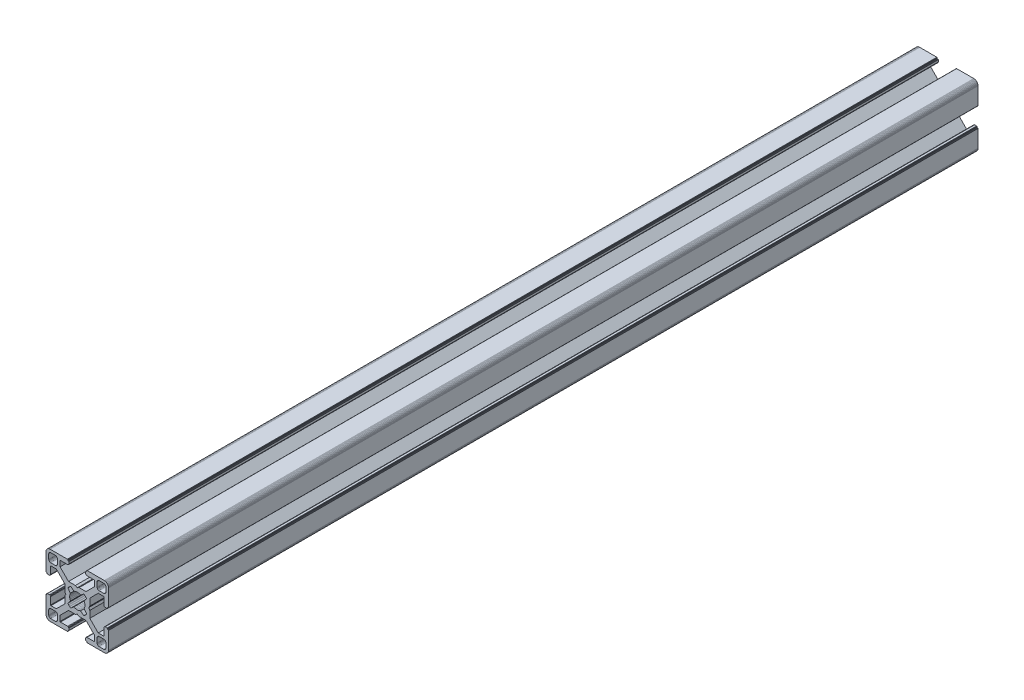
SolidWorks part; units mm, degrees
ref_plane "Front Plane" through (0, 0, 0) normal (0, 0, 1) x (1, 0, 0)
ref_plane "Top Plane" through (0, 0, 0) normal (0, 1, 0) x (1, 0, 0)
ref_plane "Right Plane" through (0, 0, 0) normal (1, 0, 0) x (0, 0, -1)
ref_plane "Plane1" through (0, 0, 0) normal (0, 0, 1) x (1, 0, 0)
sketch "Sketch1" plane through (0, 0, 0) normal (0, 0, 1) x (1, 0, 0)
  line L0 (28.3473, 29.9696) -> (28, 30)
  line L1 (28, 30) -> (19.75, 30)
  line L2 (19.75, 30) -> (19.7153, 29.997)
  line L3 (19.7153, 29.997) -> (19.6816, 29.9879)
  line L4 (19.6816, 29.9879) -> (19.65, 29.9732)
  line L5 (19.65, 29.9732) -> (19.6214, 29.9532)
  line L6 (19.6214, 29.9532) -> (19.5968, 29.9286)
  line L7 (19.5968, 29.9286) -> (19.5768, 29.9)
  line L8 (19.5768, 29.9) -> (19.5621, 29.8684)
  line L9 (19.5621, 29.8684) -> (19.553, 29.8347)
  line L10 (19.553, 29.8347) -> (19.55, 29.8)
  line L11 (19.55, 29.8) -> (19.55, 29.7)
  line L12 (19.55, 29.7) -> (19.547, 29.6653)
  line L13 (19.547, 29.6653) -> (19.5379, 29.6316)
  line L14 (19.5379, 29.6316) -> (19.5232, 29.6)
  line L15 (19.5232, 29.6) -> (19.5032, 29.5714)
  line L16 (19.5032, 29.5714) -> (19.4786, 29.5468)
  line L17 (19.4786, 29.5468) -> (19.45, 29.5268)
  line L18 (19.45, 29.5268) -> (19.4184, 29.5121)
  line L19 (19.4184, 29.5121) -> (19.3847, 29.503)
  line L20 (19.3847, 29.503) -> (19.35, 29.5)
  line L21 (19.35, 29.5) -> (19.25, 29.5)
  line L22 (19.25, 29.5) -> (19.2153, 29.497)
  line L23 (19.2153, 29.497) -> (19.1816, 29.4879)
  line L24 (19.1816, 29.4879) -> (19.15, 29.4732)
  line L25 (19.15, 29.4732) -> (19.1214, 29.4532)
  line L26 (19.1214, 29.4532) -> (19.0968, 29.4286)
  line L27 (19.0968, 29.4286) -> (19.0768, 29.4)
  line L28 (19.0768, 29.4) -> (19.0621, 29.3684)
  line L29 (19.0621, 29.3684) -> (19.053, 29.3347)
  line L30 (19.053, 29.3347) -> (19.05, 29.3)
  line L31 (19.05, 29.3) -> (19.05, 28.4)
  line L32 (19.05, 28.4) -> (19.0591, 28.2958)
  line L33 (19.0591, 28.2958) -> (19.0862, 28.1948)
  line L34 (19.0862, 28.1948) -> (19.1304, 28.1)
  line L35 (19.1304, 28.1) -> (19.1904, 28.0143)
  line L36 (19.1904, 28.0143) -> (19.2643, 27.9404)
  line L37 (19.2643, 27.9404) -> (19.35, 27.8804)
  line L38 (19.35, 27.8804) -> (19.4448, 27.8362)
  line L39 (19.4448, 27.8362) -> (19.5458, 27.8091)
  line L40 (19.5458, 27.8091) -> (19.65, 27.8)
  line L41 (19.65, 27.8) -> (23.05, 27.8)
  line L42 (23.05, 27.8) -> (23.0847, 27.7969)
  line L43 (23.0847, 27.7969) -> (23.1184, 27.7879)
  line L44 (23.1184, 27.7879) -> (23.15, 27.7732)
  line L45 (23.15, 27.7732) -> (23.1786, 27.7532)
  line L46 (23.1786, 27.7532) -> (23.2032, 27.7285)
  line L47 (23.2032, 27.7285) -> (23.2232, 27.7)
  line L48 (23.2232, 27.7) -> (23.2379, 27.6684)
  line L49 (23.2379, 27.6684) -> (23.247, 27.6347)
  line L50 (23.247, 27.6347) -> (23.25, 27.6)
  line L51 (23.25, 27.6) -> (23.25, 25.05)
  line L52 (23.25, 25.05) -> (19.2045, 21)
  line L53 (19.2045, 21) -> (15.9, 21)
  line L54 (15.9, 21) -> (15, 20.4848)
  line L55 (15, 20.4848) -> (14.1, 21)
  line L56 (14.1, 21) -> (10.7955, 21)
  line L57 (10.7955, 21) -> (7.9973, 23.8013)
  line L58 (7.9973, 23.8013) -> (6.75, 25.05)
  line L59 (6.75, 25.05) -> (6.75, 27.6)
  line L60 (6.75, 27.6) -> (6.753, 27.6347)
  line L61 (6.753, 27.6347) -> (6.7621, 27.6684)
  line L62 (6.7621, 27.6684) -> (6.7768, 27.7)
  line L63 (6.7768, 27.7) -> (6.7968, 27.7285)
  line L64 (6.7968, 27.7285) -> (6.8215, 27.7532)
  line L65 (6.8215, 27.7532) -> (6.85, 27.7732)
  line L66 (6.85, 27.7732) -> (6.8816, 27.7879)
  line L67 (6.8816, 27.7879) -> (6.9153, 27.7969)
  line L68 (6.9153, 27.7969) -> (6.95, 27.8)
  line L69 (6.95, 27.8) -> (10.35, 27.8)
  line L70 (10.35, 27.8) -> (10.4542, 27.8091)
  line L71 (10.4542, 27.8091) -> (10.5552, 27.8362)
  line L72 (10.5552, 27.8362) -> (10.65, 27.8804)
  line L73 (10.65, 27.8804) -> (10.7357, 27.9404)
  line L74 (10.7357, 27.9404) -> (10.8096, 28.0143)
  line L75 (10.8096, 28.0143) -> (10.8696, 28.1)
  line L76 (10.8696, 28.1) -> (10.9138, 28.1948)
  line L77 (10.9138, 28.1948) -> (10.9409, 28.2958)
  line L78 (10.9409, 28.2958) -> (10.95, 28.4)
  line L79 (10.95, 28.4) -> (10.95, 29.3)
  line L80 (10.95, 29.3) -> (10.947, 29.3347)
  line L81 (10.947, 29.3347) -> (10.938, 29.3684)
  line L82 (10.938, 29.3684) -> (10.9232, 29.4)
  line L83 (10.9232, 29.4) -> (10.9032, 29.4286)
  line L84 (10.9032, 29.4286) -> (10.8786, 29.4532)
  line L85 (10.8786, 29.4532) -> (10.85, 29.4732)
  line L86 (10.85, 29.4732) -> (10.8184, 29.4879)
  line L87 (10.8184, 29.4879) -> (10.7847, 29.497)
  line L88 (10.7847, 29.497) -> (10.75, 29.5)
  line L89 (10.75, 29.5) -> (10.65, 29.5)
  line L90 (10.65, 29.5) -> (10.6153, 29.503)
  line L91 (10.6153, 29.503) -> (10.5816, 29.5121)
  line L92 (10.5816, 29.5121) -> (10.55, 29.5268)
  line L93 (10.55, 29.5268) -> (10.5214, 29.5468)
  line L94 (10.5214, 29.5468) -> (10.4968, 29.5714)
  line L95 (10.4968, 29.5714) -> (10.4768, 29.6)
  line L96 (10.4768, 29.6) -> (10.4621, 29.6316)
  line L97 (10.4621, 29.6316) -> (10.453, 29.6653)
  line L98 (10.453, 29.6653) -> (10.45, 29.7)
  line L99 (10.45, 29.7) -> (10.45, 29.8)
  line L100 (10.45, 29.8) -> (10.447, 29.8347)
  line L101 (10.447, 29.8347) -> (10.4379, 29.8684)
  line L102 (10.4379, 29.8684) -> (10.4232, 29.9)
  line L103 (10.4232, 29.9) -> (10.4032, 29.9286)
  line L104 (10.4032, 29.9286) -> (10.3786, 29.9532)
  line L105 (10.3786, 29.9532) -> (10.35, 29.9732)
  line L106 (10.35, 29.9732) -> (10.3184, 29.9879)
  line L107 (10.3184, 29.9879) -> (10.2847, 29.997)
  line L108 (10.2847, 29.997) -> (10.25, 30)
  line L109 (10.25, 30) -> (2, 30)
  line L110 (2, 30) -> (1.6527, 29.9696)
  line L111 (1.6527, 29.9696) -> (1.316, 29.8794)
  line L112 (1.316, 29.8794) -> (1, 29.7321)
  line L113 (1, 29.7321) -> (0.7144, 29.5321)
  line L114 (0.7144, 29.5321) -> (0.4679, 29.2856)
  line L115 (0.4679, 29.2856) -> (0.2679, 29)
  line L116 (0.2679, 29) -> (0.1206, 28.684)
  line L117 (0.1206, 28.684) -> (0.0304, 28.3473)
  line L118 (0.0304, 28.3473) -> (0, 28)
  line L119 (0, 28) -> (0, 19.75)
  line L120 (0, 19.75) -> (0.003, 19.7153)
  line L121 (0.003, 19.7153) -> (0.0121, 19.6816)
  line L122 (0.0121, 19.6816) -> (0.0268, 19.65)
  line L123 (0.0268, 19.65) -> (0.0468, 19.6214)
  line L124 (0.0468, 19.6214) -> (0.0714, 19.5968)
  line L125 (0.0714, 19.5968) -> (0.1, 19.5768)
  line L126 (0.1, 19.5768) -> (0.1316, 19.5621)
  line L127 (0.1316, 19.5621) -> (0.1653, 19.553)
  line L128 (0.1653, 19.553) -> (0.2, 19.55)
  line L129 (0.2, 19.55) -> (0.3, 19.55)
  line L130 (0.3, 19.55) -> (0.3347, 19.547)
  line L131 (0.3347, 19.547) -> (0.3684, 19.5379)
  line L132 (0.3684, 19.5379) -> (0.4, 19.5232)
  line L133 (0.4, 19.5232) -> (0.4286, 19.5032)
  line L134 (0.4286, 19.5032) -> (0.4532, 19.4786)
  line L135 (0.4532, 19.4786) -> (0.4732, 19.45)
  line L136 (0.4732, 19.45) -> (0.4879, 19.4184)
  line L137 (0.4879, 19.4184) -> (0.497, 19.3847)
  line L138 (0.497, 19.3847) -> (0.5, 19.35)
  line L139 (0.5, 19.35) -> (0.5, 19.25)
  line L140 (0.5, 19.25) -> (0.503, 19.2153)
  line L141 (0.503, 19.2153) -> (0.5121, 19.1816)
  line L142 (0.5121, 19.1816) -> (0.5268, 19.15)
  line L143 (0.5268, 19.15) -> (0.5468, 19.1214)
  line L144 (0.5468, 19.1214) -> (0.5714, 19.0968)
  line L145 (0.5714, 19.0968) -> (0.6, 19.0768)
  line L146 (0.6, 19.0768) -> (0.6316, 19.0621)
  line L147 (0.6316, 19.0621) -> (0.6653, 19.053)
  line L148 (0.6653, 19.053) -> (0.7, 19.05)
  line L149 (0.7, 19.05) -> (1.6, 19.05)
  line L150 (1.6, 19.05) -> (1.7042, 19.0591)
  line L151 (1.7042, 19.0591) -> (1.8052, 19.0862)
  line L152 (1.8052, 19.0862) -> (1.9, 19.1304)
  line L153 (1.9, 19.1304) -> (1.9857, 19.1904)
  line L154 (1.9857, 19.1904) -> (2.0596, 19.2643)
  line L155 (2.0596, 19.2643) -> (2.1196, 19.35)
  line L156 (2.1196, 19.35) -> (2.1638, 19.4448)
  line L157 (2.1638, 19.4448) -> (2.1909, 19.5458)
  line L158 (2.1909, 19.5458) -> (2.2, 19.65)
  line L159 (2.2, 19.65) -> (2.2, 23.05)
  line L160 (2.2, 23.05) -> (2.203, 23.0847)
  line L161 (2.203, 23.0847) -> (2.2121, 23.1184)
  line L162 (2.2121, 23.1184) -> (2.2268, 23.15)
  line L163 (2.2268, 23.15) -> (2.2468, 23.1786)
  line L164 (2.2468, 23.1786) -> (2.2714, 23.2032)
  line L165 (2.2714, 23.2032) -> (2.3, 23.2232)
  line L166 (2.3, 23.2232) -> (2.3316, 23.2379)
  line L167 (2.3316, 23.2379) -> (2.3653, 23.247)
  line L168 (2.3653, 23.247) -> (2.4, 23.25)
  line L169 (2.4, 23.25) -> (4.95, 23.25)
  line L170 (4.95, 23.25) -> (7.9973, 20.2027)
  line L171 (7.9973, 20.2027) -> (8.9955, 19.2045)
  line L172 (8.9955, 19.2045) -> (8.9955, 15.9)
  line L173 (8.9955, 15.9) -> (9.5151, 15)
  line L174 (9.5151, 15) -> (8.9955, 14.1)
  line L175 (8.9955, 14.1) -> (8.9955, 10.7955)
  line L176 (8.9955, 10.7955) -> (4.95, 6.75)
  line L177 (4.95, 6.75) -> (2.4, 6.75)
  line L178 (2.4, 6.75) -> (2.3653, 6.753)
  line L179 (2.3653, 6.753) -> (2.3316, 6.7621)
  line L180 (2.3316, 6.7621) -> (2.3, 6.7768)
  line L181 (2.3, 6.7768) -> (2.2714, 6.7968)
  line L182 (2.2714, 6.7968) -> (2.2468, 6.8214)
  line L183 (2.2468, 6.8214) -> (2.2268, 6.85)
  line L184 (2.2268, 6.85) -> (2.2121, 6.8816)
  line L185 (2.2121, 6.8816) -> (2.203, 6.9153)
  line L186 (2.203, 6.9153) -> (2.2, 6.95)
  line L187 (2.2, 6.95) -> (2.2, 10.35)
  line L188 (2.2, 10.35) -> (2.1909, 10.4542)
  line L189 (2.1909, 10.4542) -> (2.1638, 10.5552)
  line L190 (2.1638, 10.5552) -> (2.1196, 10.65)
  line L191 (2.1196, 10.65) -> (2.0596, 10.7357)
  line L192 (2.0596, 10.7357) -> (1.9857, 10.8096)
  line L193 (1.9857, 10.8096) -> (1.9, 10.8696)
  line L194 (1.9, 10.8696) -> (1.8052, 10.9138)
  line L195 (1.8052, 10.9138) -> (1.7042, 10.9409)
  line L196 (1.7042, 10.9409) -> (1.6, 10.95)
  line L197 (1.6, 10.95) -> (0.7, 10.95)
  line L198 (0.7, 10.95) -> (0.6653, 10.9469)
  line L199 (0.6653, 10.9469) -> (0.6316, 10.9379)
  line L200 (0.6316, 10.9379) -> (0.6, 10.9232)
  line L201 (0.6, 10.9232) -> (0.5715, 10.9032)
  line L202 (0.5715, 10.9032) -> (0.5468, 10.8785)
  line L203 (0.5468, 10.8785) -> (0.5268, 10.85)
  line L204 (0.5268, 10.85) -> (0.5121, 10.8184)
  line L205 (0.5121, 10.8184) -> (0.503, 10.7847)
  line L206 (0.503, 10.7847) -> (0.5, 10.75)
  line L207 (0.5, 10.75) -> (0.5, 10.65)
  line L208 (0.5, 10.65) -> (0.497, 10.6153)
  line L209 (0.497, 10.6153) -> (0.4879, 10.5816)
  line L210 (0.4879, 10.5816) -> (0.4732, 10.55)
  line L211 (0.4732, 10.55) -> (0.4532, 10.5214)
  line L212 (0.4532, 10.5214) -> (0.4286, 10.4968)
  line L213 (0.4286, 10.4968) -> (0.4, 10.4768)
  line L214 (0.4, 10.4768) -> (0.3684, 10.4621)
  line L215 (0.3684, 10.4621) -> (0.3347, 10.453)
  line L216 (0.3347, 10.453) -> (0.3, 10.45)
  line L217 (0.3, 10.45) -> (0.2, 10.45)
  line L218 (0.2, 10.45) -> (0.1653, 10.447)
  line L219 (0.1653, 10.447) -> (0.1316, 10.4379)
  line L220 (0.1316, 10.4379) -> (0.1, 10.4232)
  line L221 (0.1, 10.4232) -> (0.0714, 10.4032)
  line L222 (0.0714, 10.4032) -> (0.0468, 10.3786)
  line L223 (0.0468, 10.3786) -> (0.0268, 10.35)
  line L224 (0.0268, 10.35) -> (0.0121, 10.3184)
  line L225 (0.0121, 10.3184) -> (0.003, 10.2847)
  line L226 (0.003, 10.2847) -> (0, 10.25)
  line L227 (0, 10.25) -> (0, 2)
  line L228 (0, 2) -> (0.0304, 1.6527)
  line L229 (0.0304, 1.6527) -> (0.1206, 1.316)
  line L230 (0.1206, 1.316) -> (0.2679, 1)
  line L231 (0.2679, 1) -> (0.4679, 0.7144)
  line L232 (0.4679, 0.7144) -> (0.7144, 0.4679)
  line L233 (0.7144, 0.4679) -> (1, 0.2679)
  line L234 (1, 0.2679) -> (1.316, 0.1206)
  line L235 (1.316, 0.1206) -> (1.6527, 0.0304)
  line L236 (1.6527, 0.0304) -> (2, 0)
  line L237 (2, 0) -> (10.25, 0)
  line L238 (10.25, 0) -> (10.2847, 0.003)
  line L239 (10.2847, 0.003) -> (10.3184, 0.0121)
  line L240 (10.3184, 0.0121) -> (10.35, 0.0268)
  line L241 (10.35, 0.0268) -> (10.3786, 0.0468)
  line L242 (10.3786, 0.0468) -> (10.4032, 0.0714)
  line L243 (10.4032, 0.0714) -> (10.4232, 0.1)
  line L244 (10.4232, 0.1) -> (10.4379, 0.1316)
  line L245 (10.4379, 0.1316) -> (10.447, 0.1653)
  line L246 (10.447, 0.1653) -> (10.45, 0.2)
  line L247 (10.45, 0.2) -> (10.45, 0.3)
  line L248 (10.45, 0.3) -> (10.453, 0.3347)
  line L249 (10.453, 0.3347) -> (10.4621, 0.3684)
  line L250 (10.4621, 0.3684) -> (10.4768, 0.4)
  line L251 (10.4768, 0.4) -> (10.4968, 0.4286)
  line L252 (10.4968, 0.4286) -> (10.5214, 0.4532)
  line L253 (10.5214, 0.4532) -> (10.55, 0.4732)
  line L254 (10.55, 0.4732) -> (10.5816, 0.4879)
  line L255 (10.5816, 0.4879) -> (10.6153, 0.497)
  line L256 (10.6153, 0.497) -> (10.65, 0.5)
  line L257 (10.65, 0.5) -> (10.75, 0.5)
  line L258 (10.75, 0.5) -> (10.7847, 0.503)
  line L259 (10.7847, 0.503) -> (10.8184, 0.5121)
  line L260 (10.8184, 0.5121) -> (10.85, 0.5268)
  line L261 (10.85, 0.5268) -> (10.8785, 0.5468)
  line L262 (10.8785, 0.5468) -> (10.9032, 0.5715)
  line L263 (10.9032, 0.5715) -> (10.9232, 0.6)
  line L264 (10.9232, 0.6) -> (10.9379, 0.6316)
  line L265 (10.9379, 0.6316) -> (10.9469, 0.6653)
  line L266 (10.9469, 0.6653) -> (10.95, 0.7)
  line L267 (10.95, 0.7) -> (10.95, 1.6)
  line L268 (10.95, 1.6) -> (10.9409, 1.7042)
  line L269 (10.9409, 1.7042) -> (10.9138, 1.8052)
  line L270 (10.9138, 1.8052) -> (10.8696, 1.9)
  line L271 (10.8696, 1.9) -> (10.8096, 1.9857)
  line L272 (10.8096, 1.9857) -> (10.7357, 2.0596)
  line L273 (10.7357, 2.0596) -> (10.65, 2.1196)
  line L274 (10.65, 2.1196) -> (10.5552, 2.1638)
  line L275 (10.5552, 2.1638) -> (10.4542, 2.1909)
  line L276 (10.4542, 2.1909) -> (10.35, 2.2)
  line L277 (10.35, 2.2) -> (6.95, 2.2)
  line L278 (6.95, 2.2) -> (6.9153, 2.203)
  line L279 (6.9153, 2.203) -> (6.8816, 2.212)
  line L280 (6.8816, 2.212) -> (6.85, 2.2268)
  line L281 (6.85, 2.2268) -> (6.8215, 2.2468)
  line L282 (6.8215, 2.2468) -> (6.7968, 2.2714)
  line L283 (6.7968, 2.2714) -> (6.7768, 2.3)
  line L284 (6.7768, 2.3) -> (6.7621, 2.3316)
  line L285 (6.7621, 2.3316) -> (6.753, 2.3653)
  line L286 (6.753, 2.3653) -> (6.75, 2.4)
  line L287 (6.75, 2.4) -> (6.75, 4.95)
  line L288 (6.75, 4.95) -> (9.7875, 7.9908)
  line L289 (9.7875, 7.9908) -> (10.7955, 9)
  line L290 (10.7955, 9) -> (14.1, 9)
  line L291 (14.1, 9) -> (15, 9.5151)
  line L292 (15, 9.5151) -> (15.9, 9)
  line L293 (15.9, 9) -> (19.2045, 9)
  line L294 (19.2045, 9) -> (20.2126, 7.9908)
  line L295 (20.2126, 7.9908) -> (23.25, 4.95)
  line L296 (23.25, 4.95) -> (23.25, 2.4)
  line L297 (23.25, 2.4) -> (23.247, 2.3653)
  line L298 (23.247, 2.3653) -> (23.2379, 2.3316)
  line L299 (23.2379, 2.3316) -> (23.2232, 2.3)
  line L300 (23.2232, 2.3) -> (23.2032, 2.2714)
  line L301 (23.2032, 2.2714) -> (23.1786, 2.2468)
  line L302 (23.1786, 2.2468) -> (23.15, 2.2268)
  line L303 (23.15, 2.2268) -> (23.1184, 2.212)
  line L304 (23.1184, 2.212) -> (23.0847, 2.203)
  line L305 (23.0847, 2.203) -> (23.05, 2.2)
  line L306 (23.05, 2.2) -> (19.65, 2.2)
  line L307 (19.65, 2.2) -> (19.5458, 2.1909)
  line L308 (19.5458, 2.1909) -> (19.4448, 2.1638)
  line L309 (19.4448, 2.1638) -> (19.35, 2.1196)
  line L310 (19.35, 2.1196) -> (19.2643, 2.0596)
  line L311 (19.2643, 2.0596) -> (19.1904, 1.9857)
  line L312 (19.1904, 1.9857) -> (19.1304, 1.9)
  line L313 (19.1304, 1.9) -> (19.0862, 1.8052)
  line L314 (19.0862, 1.8052) -> (19.0591, 1.7042)
  line L315 (19.0591, 1.7042) -> (19.05, 1.6)
  line L316 (19.05, 1.6) -> (19.05, 0.7)
  line L317 (19.05, 0.7) -> (19.053, 0.6653)
  line L318 (19.053, 0.6653) -> (19.0621, 0.6316)
  line L319 (19.0621, 0.6316) -> (19.0768, 0.6)
  line L320 (19.0768, 0.6) -> (19.0968, 0.5714)
  line L321 (19.0968, 0.5714) -> (19.1214, 0.5468)
  line L322 (19.1214, 0.5468) -> (19.15, 0.5268)
  line L323 (19.15, 0.5268) -> (19.1816, 0.5121)
  line L324 (19.1816, 0.5121) -> (19.2153, 0.503)
  line L325 (19.2153, 0.503) -> (19.25, 0.5)
  line L326 (19.25, 0.5) -> (19.35, 0.5)
  line L327 (19.35, 0.5) -> (19.3847, 0.497)
  line L328 (19.3847, 0.497) -> (19.4184, 0.4879)
  line L329 (19.4184, 0.4879) -> (19.45, 0.4732)
  line L330 (19.45, 0.4732) -> (19.4786, 0.4532)
  line L331 (19.4786, 0.4532) -> (19.5032, 0.4286)
  line L332 (19.5032, 0.4286) -> (19.5232, 0.4)
  line L333 (19.5232, 0.4) -> (19.5379, 0.3684)
  line L334 (19.5379, 0.3684) -> (19.547, 0.3347)
  line L335 (19.547, 0.3347) -> (19.55, 0.3)
  line L336 (19.55, 0.3) -> (19.55, 0.2)
  line L337 (19.55, 0.2) -> (19.553, 0.1653)
  line L338 (19.553, 0.1653) -> (19.5621, 0.1316)
  line L339 (19.5621, 0.1316) -> (19.5768, 0.1)
  line L340 (19.5768, 0.1) -> (19.5968, 0.0714)
  line L341 (19.5968, 0.0714) -> (19.6214, 0.0468)
  line L342 (19.6214, 0.0468) -> (19.65, 0.0268)
  line L343 (19.65, 0.0268) -> (19.6816, 0.0121)
  line L344 (19.6816, 0.0121) -> (19.7153, 0.003)
  line L345 (19.7153, 0.003) -> (19.75, 0)
  line L346 (19.75, 0) -> (28, 0)
  line L347 (28, 0) -> (28.3473, 0.0304)
  line L348 (28.3473, 0.0304) -> (28.684, 0.1206)
  line L349 (28.684, 0.1206) -> (29, 0.2679)
  line L350 (29, 0.2679) -> (29.2856, 0.4679)
  line L351 (29.2856, 0.4679) -> (29.5321, 0.7144)
  line L352 (29.5321, 0.7144) -> (29.7321, 1)
  line L353 (29.7321, 1) -> (29.8794, 1.316)
  line L354 (29.8794, 1.316) -> (29.9696, 1.6527)
  line L355 (29.9696, 1.6527) -> (30, 2)
  line L356 (30, 2) -> (30, 10.25)
  line L357 (30, 10.25) -> (29.997, 10.2847)
  line L358 (29.997, 10.2847) -> (29.988, 10.3184)
  line L359 (29.988, 10.3184) -> (29.9732, 10.35)
  line L360 (29.9732, 10.35) -> (29.9532, 10.3785)
  line L361 (29.9532, 10.3785) -> (29.9286, 10.4032)
  line L362 (29.9286, 10.4032) -> (29.9, 10.4232)
  line L363 (29.9, 10.4232) -> (29.8684, 10.4379)
  line L364 (29.8684, 10.4379) -> (29.8347, 10.447)
  line L365 (29.8347, 10.447) -> (29.8, 10.45)
  line L366 (29.8, 10.45) -> (29.7, 10.45)
  line L367 (29.7, 10.45) -> (29.6649, 10.4534)
  line L368 (29.6649, 10.4534) -> (29.6312, 10.4624)
  line L369 (29.6312, 10.4624) -> (29.5996, 10.4772)
  line L370 (29.5996, 10.4772) -> (29.5711, 10.4972)
  line L371 (29.5711, 10.4972) -> (29.5464, 10.5218)
  line L372 (29.5464, 10.5218) -> (29.5264, 10.5504)
  line L373 (29.5264, 10.5504) -> (29.5117, 10.582)
  line L374 (29.5117, 10.582) -> (29.5027, 10.6156)
  line L375 (29.5027, 10.6156) -> (29.4996, 10.6504)
  line L376 (29.4996, 10.6504) -> (29.4996, 10.7504)
  line L377 (29.4996, 10.7504) -> (29.497, 10.7847)
  line L378 (29.497, 10.7847) -> (29.4879, 10.8184)
  line L379 (29.4879, 10.8184) -> (29.4732, 10.85)
  line L380 (29.4732, 10.85) -> (29.4532, 10.8785)
  line L381 (29.4532, 10.8785) -> (29.4286, 10.9032)
  line L382 (29.4286, 10.9032) -> (29.4, 10.9232)
  line L383 (29.4, 10.9232) -> (29.3684, 10.9379)
  line L384 (29.3684, 10.9379) -> (29.3347, 10.9469)
  line L385 (29.3347, 10.9469) -> (29.3, 10.95)
  line L386 (29.3, 10.95) -> (28.4, 10.95)
  line L387 (28.4, 10.95) -> (28.2958, 10.9409)
  line L388 (28.2958, 10.9409) -> (28.1948, 10.9138)
  line L389 (28.1948, 10.9138) -> (28.1, 10.8696)
  line L390 (28.1, 10.8696) -> (28.0143, 10.8096)
  line L391 (28.0143, 10.8096) -> (27.9404, 10.7357)
  line L392 (27.9404, 10.7357) -> (27.8804, 10.65)
  line L393 (27.8804, 10.65) -> (27.8362, 10.5552)
  line L394 (27.8362, 10.5552) -> (27.8091, 10.4542)
  line L395 (27.8091, 10.4542) -> (27.8, 10.35)
  line L396 (27.8, 10.35) -> (27.8, 6.95)
  line L397 (27.8, 6.95) -> (27.797, 6.9153)
  line L398 (27.797, 6.9153) -> (27.7879, 6.8816)
  line L399 (27.7879, 6.8816) -> (27.7732, 6.85)
  line L400 (27.7732, 6.85) -> (27.7532, 6.8214)
  line L401 (27.7532, 6.8214) -> (27.7286, 6.7968)
  line L402 (27.7286, 6.7968) -> (27.7, 6.7768)
  line L403 (27.7, 6.7768) -> (27.6684, 6.7621)
  line L404 (27.6684, 6.7621) -> (27.6347, 6.753)
  line L405 (27.6347, 6.753) -> (27.6, 6.75)
  line L406 (27.6, 6.75) -> (25.05, 6.75)
  line L407 (25.05, 6.75) -> (23.8092, 7.9908)
  line L408 (23.8092, 7.9908) -> (21.0045, 10.7955)
  line L409 (21.0045, 10.7955) -> (21.0045, 14.1)
  line L410 (21.0045, 14.1) -> (20.4849, 15)
  line L411 (20.4849, 15) -> (21.0045, 15.9)
  line L412 (21.0045, 15.9) -> (21.0045, 19.2045)
  line L413 (21.0045, 19.2045) -> (25.05, 23.25)
  line L414 (25.05, 23.25) -> (27.6, 23.25)
  line L415 (27.6, 23.25) -> (27.6347, 23.247)
  line L416 (27.6347, 23.247) -> (27.6684, 23.2379)
  line L417 (27.6684, 23.2379) -> (27.7, 23.2232)
  line L418 (27.7, 23.2232) -> (27.7286, 23.2032)
  line L419 (27.7286, 23.2032) -> (27.7532, 23.1786)
  line L420 (27.7532, 23.1786) -> (27.7732, 23.15)
  line L421 (27.7732, 23.15) -> (27.7879, 23.1184)
  line L422 (27.7879, 23.1184) -> (27.797, 23.0847)
  line L423 (27.797, 23.0847) -> (27.8, 23.05)
  line L424 (27.8, 23.05) -> (27.8, 19.65)
  line L425 (27.8, 19.65) -> (27.8091, 19.5458)
  line L426 (27.8091, 19.5458) -> (27.8362, 19.4448)
  line L427 (27.8362, 19.4448) -> (27.8804, 19.35)
  line L428 (27.8804, 19.35) -> (27.9404, 19.2643)
  line L429 (27.9404, 19.2643) -> (28.0143, 19.1904)
  line L430 (28.0143, 19.1904) -> (28.1, 19.1304)
  line L431 (28.1, 19.1304) -> (28.1948, 19.0862)
  line L432 (28.1948, 19.0862) -> (28.2958, 19.0591)
  line L433 (28.2958, 19.0591) -> (28.4, 19.05)
  line L434 (28.4, 19.05) -> (29.3, 19.05)
  line L435 (29.3, 19.05) -> (29.3347, 19.053)
  line L436 (29.3347, 19.053) -> (29.3684, 19.0621)
  line L437 (29.3684, 19.0621) -> (29.4, 19.0768)
  line L438 (29.4, 19.0768) -> (29.4282, 19.0971)
  line L439 (29.4282, 19.0971) -> (29.4528, 19.1218)
  line L440 (29.4528, 19.1218) -> (29.4728, 19.1504)
  line L441 (29.4728, 19.1504) -> (29.4876, 19.182)
  line L442 (29.4876, 19.182) -> (29.4966, 19.2156)
  line L443 (29.4966, 19.2156) -> (29.4996, 19.2504)
  line L444 (29.4996, 19.2504) -> (29.4996, 19.3504)
  line L445 (29.4996, 19.3504) -> (29.5027, 19.3851)
  line L446 (29.5027, 19.3851) -> (29.5117, 19.4188)
  line L447 (29.5117, 19.4188) -> (29.5264, 19.4504)
  line L448 (29.5264, 19.4504) -> (29.5464, 19.4789)
  line L449 (29.5464, 19.4789) -> (29.5711, 19.5036)
  line L450 (29.5711, 19.5036) -> (29.5996, 19.5236)
  line L451 (29.5996, 19.5236) -> (29.6312, 19.5383)
  line L452 (29.6312, 19.5383) -> (29.6649, 19.5473)
  line L453 (29.6649, 19.5473) -> (29.7, 19.55)
  line L454 (29.7, 19.55) -> (29.8, 19.55)
  line L455 (29.8, 19.55) -> (29.8347, 19.553)
  line L456 (29.8347, 19.553) -> (29.8684, 19.5621)
  line L457 (29.8684, 19.5621) -> (29.9, 19.5768)
  line L458 (29.9, 19.5768) -> (29.9286, 19.5968)
  line L459 (29.9286, 19.5968) -> (29.9532, 19.6214)
  line L460 (29.9532, 19.6214) -> (29.9732, 19.65)
  line L461 (29.9732, 19.65) -> (29.9879, 19.6816)
  line L462 (29.9879, 19.6816) -> (29.997, 19.7153)
  line L463 (29.997, 19.7153) -> (30, 19.75)
  line L464 (30, 19.75) -> (30, 28)
  line L465 (30, 28) -> (29.9696, 28.3473)
  line L466 (29.9696, 28.3473) -> (29.8794, 28.684)
  line L467 (29.8794, 28.684) -> (29.7321, 29)
  line L468 (29.7321, 29) -> (29.5321, 29.2856)
  line L469 (29.5321, 29.2856) -> (29.2856, 29.5321)
  line L470 (29.2856, 29.5321) -> (29, 29.7321)
  line L471 (29, 29.7321) -> (28.684, 29.8794)
  line L472 (28.684, 29.8794) -> (28.3473, 29.9696)
  line L473 (1.3, 25.5) -> (1.3, 27.7)
  line L474 (1.3, 27.7) -> (1.3123, 27.8564)
  line L475 (1.3123, 27.8564) -> (1.3489, 28.009)
  line L476 (1.3489, 28.009) -> (1.409, 28.154)
  line L477 (1.409, 28.154) -> (1.491, 28.2878)
  line L478 (1.491, 28.2878) -> (1.5929, 28.4071)
  line L479 (1.5929, 28.4071) -> (1.7122, 28.509)
  line L480 (1.7122, 28.509) -> (1.846, 28.591)
  line L481 (1.846, 28.591) -> (1.991, 28.6511)
  line L482 (1.991, 28.6511) -> (2.1436, 28.6877)
  line L483 (2.1436, 28.6877) -> (2.3, 28.7)
  line L484 (2.3, 28.7) -> (4.5, 28.7)
  line L485 (4.5, 28.7) -> (4.6564, 28.6877)
  line L486 (4.6564, 28.6877) -> (4.809, 28.6511)
  line L487 (4.809, 28.6511) -> (4.954, 28.591)
  line L488 (4.954, 28.591) -> (5.0878, 28.509)
  line L489 (5.0878, 28.509) -> (5.2071, 28.4071)
  line L490 (5.2071, 28.4071) -> (5.309, 28.2878)
  line L491 (5.309, 28.2878) -> (5.391, 28.154)
  line L492 (5.391, 28.154) -> (5.4511, 28.009)
  line L493 (5.4511, 28.009) -> (5.4877, 27.8564)
  line L494 (5.4877, 27.8564) -> (5.5, 27.7)
  line L495 (5.5, 27.7) -> (5.5, 25.5)
  line L496 (5.5, 25.5) -> (5.4877, 25.3436)
  line L497 (5.4877, 25.3436) -> (5.4511, 25.191)
  line L498 (5.4511, 25.191) -> (5.391, 25.046)
  line L499 (5.391, 25.046) -> (5.309, 24.9122)
  line L500 (5.309, 24.9122) -> (5.2071, 24.7929)
  line L501 (5.2071, 24.7929) -> (5.0878, 24.691)
  line L502 (5.0878, 24.691) -> (4.954, 24.609)
  line L503 (4.954, 24.609) -> (4.809, 24.5489)
  line L504 (4.809, 24.5489) -> (4.6564, 24.5123)
  line L505 (4.6564, 24.5123) -> (4.5, 24.5)
  line L506 (4.5, 24.5) -> (2.3, 24.5)
  line L507 (2.3, 24.5) -> (2.1436, 24.5123)
  line L508 (2.1436, 24.5123) -> (1.991, 24.5489)
  line L509 (1.991, 24.5489) -> (1.846, 24.609)
  line L510 (1.846, 24.609) -> (1.7122, 24.691)
  line L511 (1.7122, 24.691) -> (1.5929, 24.7929)
  line L512 (1.5929, 24.7929) -> (1.491, 24.9122)
  line L513 (1.491, 24.9122) -> (1.409, 25.046)
  line L514 (1.409, 25.046) -> (1.3489, 25.191)
  line L515 (1.3489, 25.191) -> (1.3123, 25.3436)
  line L516 (1.3123, 25.3436) -> (1.3, 25.5)
  line L517 (25.3436, 28.6877) -> (25.5, 28.7)
  line L518 (25.5, 28.7) -> (27.7, 28.7)
  line L519 (27.7, 28.7) -> (27.8564, 28.6877)
  line L520 (27.8564, 28.6877) -> (28.009, 28.6511)
  line L521 (28.009, 28.6511) -> (28.154, 28.591)
  line L522 (28.154, 28.591) -> (28.2878, 28.509)
  line L523 (28.2878, 28.509) -> (28.4071, 28.4071)
  line L524 (28.4071, 28.4071) -> (28.509, 28.2878)
  line L525 (28.509, 28.2878) -> (28.591, 28.154)
  line L526 (28.591, 28.154) -> (28.6511, 28.009)
  line L527 (28.6511, 28.009) -> (28.6877, 27.8564)
  line L528 (28.6877, 27.8564) -> (28.7, 27.7)
  line L529 (28.7, 27.7) -> (28.7, 25.5)
  line L530 (28.7, 25.5) -> (28.6877, 25.3436)
  line L531 (28.6877, 25.3436) -> (28.6511, 25.191)
  line L532 (28.6511, 25.191) -> (28.591, 25.046)
  line L533 (28.591, 25.046) -> (28.509, 24.9122)
  line L534 (28.509, 24.9122) -> (28.4071, 24.7929)
  line L535 (28.4071, 24.7929) -> (28.2878, 24.691)
  line L536 (28.2878, 24.691) -> (28.154, 24.609)
  line L537 (28.154, 24.609) -> (28.009, 24.5489)
  line L538 (28.009, 24.5489) -> (27.8564, 24.5123)
  line L539 (27.8564, 24.5123) -> (27.7, 24.5)
  line L540 (27.7, 24.5) -> (25.5, 24.5)
  line L541 (25.5, 24.5) -> (25.3436, 24.5123)
  line L542 (25.3436, 24.5123) -> (25.191, 24.5489)
  line L543 (25.191, 24.5489) -> (25.046, 24.609)
  line L544 (25.046, 24.609) -> (24.9122, 24.691)
  line L545 (24.9122, 24.691) -> (24.7929, 24.7929)
  line L546 (24.7929, 24.7929) -> (24.691, 24.9122)
  line L547 (24.691, 24.9122) -> (24.609, 25.046)
  line L548 (24.609, 25.046) -> (24.5489, 25.191)
  line L549 (24.5489, 25.191) -> (24.5123, 25.3436)
  line L550 (24.5123, 25.3436) -> (24.5, 25.5)
  line L551 (24.5, 25.5) -> (24.5, 27.7)
  line L552 (24.5, 27.7) -> (24.5123, 27.8564)
  line L553 (24.5123, 27.8564) -> (24.5489, 28.009)
  line L554 (24.5489, 28.009) -> (24.609, 28.154)
  line L555 (24.609, 28.154) -> (24.691, 28.2878)
  line L556 (24.691, 28.2878) -> (24.7929, 28.4071)
  line L557 (24.7929, 28.4071) -> (24.9122, 28.509)
  line L558 (24.9122, 28.509) -> (25.046, 28.591)
  line L559 (25.046, 28.591) -> (25.191, 28.6511)
  line L560 (25.191, 28.6511) -> (25.3436, 28.6877)
  line L561 (15, 18.65) -> (15.55, 18.6083)
  line L562 (15.55, 18.6083) -> (16.0875, 18.4842)
  line L563 (16.0875, 18.4842) -> (16.6001, 18.2806)
  line L564 (16.6001, 18.2806) -> (18.1359, 19.5184)
  line L565 (18.1359, 19.5184) -> (18.645, 19.1187)
  line L566 (18.645, 19.1187) -> (19.1036, 18.6621)
  line L567 (19.1036, 18.6621) -> (19.5053, 18.1547)
  line L568 (19.5053, 18.1547) -> (18.2806, 16.6001)
  line L569 (18.2806, 16.6001) -> (18.4842, 16.0875)
  line L570 (18.4842, 16.0875) -> (18.6083, 15.55)
  line L571 (18.6083, 15.55) -> (18.65, 15)
  line L572 (18.65, 15) -> (18.6083, 14.45)
  line L573 (18.6083, 14.45) -> (18.4842, 13.9125)
  line L574 (18.4842, 13.9125) -> (18.2806, 13.3999)
  line L575 (18.2806, 13.3999) -> (19.5053, 11.8453)
  line L576 (19.5053, 11.8453) -> (19.1036, 11.3379)
  line L577 (19.1036, 11.3379) -> (18.645, 10.8813)
  line L578 (18.645, 10.8813) -> (18.1359, 10.4816)
  line L579 (18.1359, 10.4816) -> (16.6001, 11.7194)
  line L580 (16.6001, 11.7194) -> (16.0875, 11.5158)
  line L581 (16.0875, 11.5158) -> (15.55, 11.3917)
  line L582 (15.55, 11.3917) -> (15, 11.35)
  line L583 (15, 11.35) -> (14.45, 11.3917)
  line L584 (14.45, 11.3917) -> (13.9125, 11.5158)
  line L585 (13.9125, 11.5158) -> (13.3999, 11.7194)
  line L586 (13.3999, 11.7194) -> (11.8641, 10.4816)
  line L587 (11.8641, 10.4816) -> (11.355, 10.8813)
  line L588 (11.355, 10.8813) -> (10.8964, 11.3379)
  line L589 (10.8964, 11.3379) -> (10.4947, 11.8453)
  line L590 (10.4947, 11.8453) -> (11.7194, 13.3999)
  line L591 (11.7194, 13.3999) -> (11.5158, 13.9125)
  line L592 (11.5158, 13.9125) -> (11.3917, 14.45)
  line L593 (11.3917, 14.45) -> (11.35, 15)
  line L594 (11.35, 15) -> (11.3917, 15.55)
  line L595 (11.3917, 15.55) -> (11.5158, 16.0875)
  line L596 (11.5158, 16.0875) -> (11.7194, 16.6001)
  line L597 (11.7194, 16.6001) -> (10.4947, 18.1547)
  line L598 (10.4947, 18.1547) -> (10.8964, 18.6621)
  line L599 (10.8964, 18.6621) -> (11.355, 19.1187)
  line L600 (11.355, 19.1187) -> (11.8641, 19.5184)
  line L601 (11.8641, 19.5184) -> (13.3999, 18.2806)
  line L602 (13.3999, 18.2806) -> (13.9125, 18.4842)
  line L603 (13.9125, 18.4842) -> (14.45, 18.6083)
  line L604 (14.45, 18.6083) -> (15, 18.65)
  line L605 (4.5, 1.3) -> (2.3, 1.3)
  line L606 (2.3, 1.3) -> (2.1436, 1.3123)
  line L607 (2.1436, 1.3123) -> (1.991, 1.3489)
  line L608 (1.991, 1.3489) -> (1.846, 1.409)
  line L609 (1.846, 1.409) -> (1.7122, 1.491)
  line L610 (1.7122, 1.491) -> (1.5929, 1.5929)
  line L611 (1.5929, 1.5929) -> (1.491, 1.7122)
  line L612 (1.491, 1.7122) -> (1.409, 1.846)
  line L613 (1.409, 1.846) -> (1.3489, 1.991)
  line L614 (1.3489, 1.991) -> (1.3123, 2.1436)
  line L615 (1.3123, 2.1436) -> (1.3, 2.3)
  line L616 (1.3, 2.3) -> (1.3, 4.5)
  line L617 (1.3, 4.5) -> (1.3123, 4.6564)
  line L618 (1.3123, 4.6564) -> (1.3489, 4.809)
  line L619 (1.3489, 4.809) -> (1.409, 4.954)
  line L620 (1.409, 4.954) -> (1.491, 5.0878)
  line L621 (1.491, 5.0878) -> (1.5929, 5.2071)
  line L622 (1.5929, 5.2071) -> (1.7122, 5.309)
  line L623 (1.7122, 5.309) -> (1.846, 5.391)
  line L624 (1.846, 5.391) -> (1.991, 5.4511)
  line L625 (1.991, 5.4511) -> (2.1436, 5.4877)
  line L626 (2.1436, 5.4877) -> (2.3, 5.5)
  line L627 (2.3, 5.5) -> (4.5, 5.5)
  line L628 (4.5, 5.5) -> (4.6564, 5.4877)
  line L629 (4.6564, 5.4877) -> (4.809, 5.4511)
  line L630 (4.809, 5.4511) -> (4.954, 5.391)
  line L631 (4.954, 5.391) -> (5.0878, 5.309)
  line L632 (5.0878, 5.309) -> (5.2071, 5.2071)
  line L633 (5.2071, 5.2071) -> (5.309, 5.0878)
  line L634 (5.309, 5.0878) -> (5.391, 4.954)
  line L635 (5.391, 4.954) -> (5.4511, 4.809)
  line L636 (5.4511, 4.809) -> (5.4877, 4.6564)
  line L637 (5.4877, 4.6564) -> (5.5, 4.5)
  line L638 (5.5, 4.5) -> (5.5, 2.3)
  line L639 (5.5, 2.3) -> (5.4877, 2.1436)
  line L640 (5.4877, 2.1436) -> (5.4511, 1.991)
  line L641 (5.4511, 1.991) -> (5.391, 1.846)
  line L642 (5.391, 1.846) -> (5.309, 1.7122)
  line L643 (5.309, 1.7122) -> (5.2071, 1.5929)
  line L644 (5.2071, 1.5929) -> (5.0878, 1.491)
  line L645 (5.0878, 1.491) -> (4.954, 1.409)
  line L646 (4.954, 1.409) -> (4.809, 1.3489)
  line L647 (4.809, 1.3489) -> (4.6564, 1.3123)
  line L648 (4.6564, 1.3123) -> (4.5, 1.3)
  line L649 (27.7, 1.3) -> (25.5, 1.3)
  line L650 (25.5, 1.3) -> (25.3436, 1.3123)
  line L651 (25.3436, 1.3123) -> (25.191, 1.3489)
  line L652 (25.191, 1.3489) -> (25.046, 1.409)
  line L653 (25.046, 1.409) -> (24.9122, 1.491)
  line L654 (24.9122, 1.491) -> (24.7929, 1.5929)
  line L655 (24.7929, 1.5929) -> (24.691, 1.7122)
  line L656 (24.691, 1.7122) -> (24.609, 1.846)
  line L657 (24.609, 1.846) -> (24.5489, 1.991)
  line L658 (24.5489, 1.991) -> (24.5123, 2.1436)
  line L659 (24.5123, 2.1436) -> (24.5, 2.3)
  line L660 (24.5, 2.3) -> (24.5, 4.5)
  line L661 (24.5, 4.5) -> (24.5123, 4.6564)
  line L662 (24.5123, 4.6564) -> (24.5489, 4.809)
  line L663 (24.5489, 4.809) -> (24.609, 4.954)
  line L664 (24.609, 4.954) -> (24.691, 5.0878)
  line L665 (24.691, 5.0878) -> (24.7929, 5.2071)
  line L666 (24.7929, 5.2071) -> (24.9122, 5.309)
  line L667 (24.9122, 5.309) -> (25.046, 5.391)
  line L668 (25.046, 5.391) -> (25.191, 5.4511)
  line L669 (25.191, 5.4511) -> (25.3436, 5.4877)
  line L670 (25.3436, 5.4877) -> (25.5, 5.5)
  line L671 (25.5, 5.5) -> (27.7, 5.5)
  line L672 (27.7, 5.5) -> (27.8564, 5.4877)
  line L673 (27.8564, 5.4877) -> (28.009, 5.4511)
  line L674 (28.009, 5.4511) -> (28.154, 5.391)
  line L675 (28.154, 5.391) -> (28.2878, 5.309)
  line L676 (28.2878, 5.309) -> (28.4071, 5.2071)
  line L677 (28.4071, 5.2071) -> (28.509, 5.0878)
  line L678 (28.509, 5.0878) -> (28.591, 4.954)
  line L679 (28.591, 4.954) -> (28.6511, 4.809)
  line L680 (28.6511, 4.809) -> (28.6877, 4.6564)
  line L681 (28.6877, 4.6564) -> (28.7, 4.5)
  line L682 (28.7, 4.5) -> (28.7, 2.3)
  line L683 (28.7, 2.3) -> (28.6877, 2.1436)
  line L684 (28.6877, 2.1436) -> (28.6511, 1.991)
  line L685 (28.6511, 1.991) -> (28.591, 1.846)
  line L686 (28.591, 1.846) -> (28.509, 1.7122)
  line L687 (28.509, 1.7122) -> (28.4071, 1.5929)
  line L688 (28.4071, 1.5929) -> (28.2878, 1.491)
  line L689 (28.2878, 1.491) -> (28.154, 1.409)
  line L690 (28.154, 1.409) -> (28.009, 1.3489)
  line L691 (28.009, 1.3489) -> (27.8564, 1.3123)
  line L692 (27.8564, 1.3123) -> (27.7, 1.3)
extrude "Boss-Extrude1" add sketch "Sketch1" against normal blind 417
